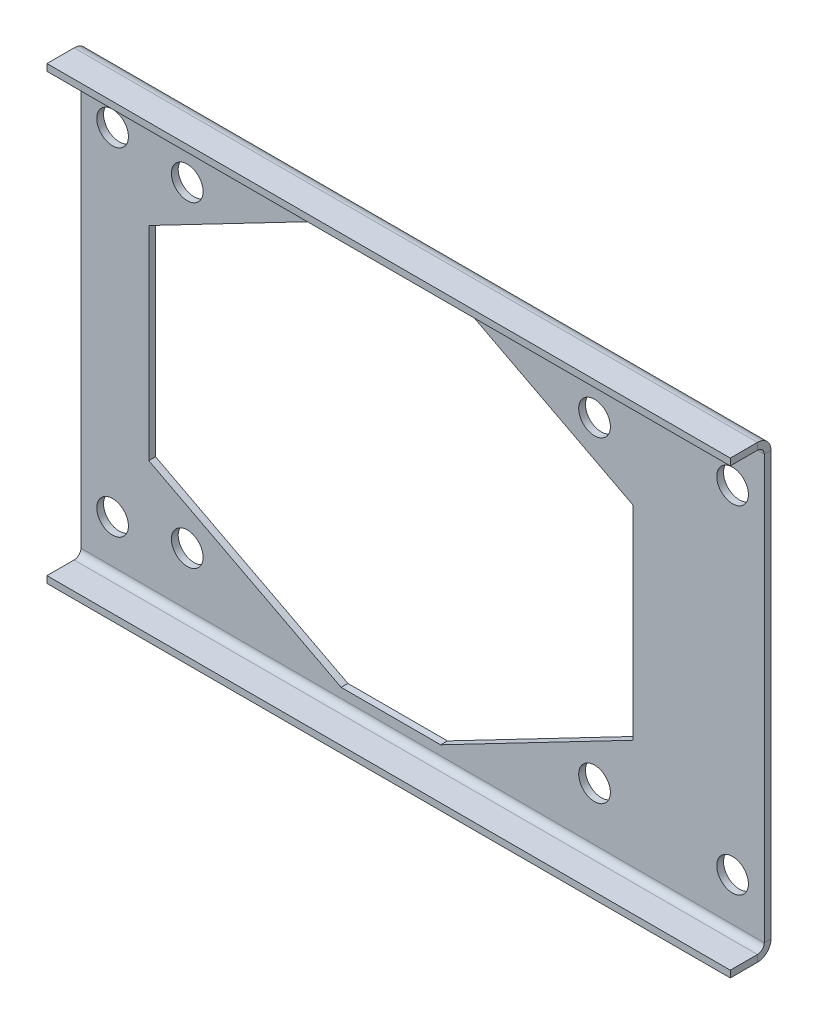
SolidWorks part; units mm, degrees
note: The reader was unsure of these and kept them because the rebuilt part matched: flange length of "Ребро-кромка1".
material "AISI 304"
ref_plane "Спереди" through (0, 0, 0) normal (0, 0, 1) x (1, 0, 0)
ref_plane "Сверху" through (0, 0, 0) normal (0, 1, 0) x (1, 0, 0)
ref_plane "Справа" through (0, 0, 0) normal (1, 0, 0) x (0, 0, -1)
sketch "Эскиз1" plane through (0, 0, 0) normal (0, 0, 1) x (1, 0, 0)
  line L0 (-151, 0) -> (151, 0)
  line L1 (-151, 0) -> (-151, 96.5)
  line L2 (-151, 96.5) -> (-121, 96.5)
  line L5 (93, 96.5) -> (151, 96.5)
  line L6 (151, 96.5) -> (151, 0)
  line L7 (-121, 96.5) -> (-121, 51.5)
  line L8 (-121, 51.5) -> (-36, 7.25)
  line L9 (-36, 7.25) -> (8, 7.25)
  line L10 (8, 7.25) -> (93, 51.5)
  line L11 (93, 51.5) -> (93, 96.5)
  dimension "D4" = 45
  dimension "D1" = 302
  dimension "D2" = 96.5
  dimension "D3" = 214
  dimension "D5" = 30
  dimension "D6" = 44
  dimension "D7" = 89.25
base flange "Базовая кромка1" sketch "Эскиз1" thickness 3 reverse thickness direction no parameters "D1"=3
edge flange "Ребро-кромка1" sketch "Эскиз8" flange angle 90 flange length 15 flange position material outside bend radius 3 thickness 3 relief rectangular parameters "D1"=2, "D6"=10
sketch "Эскиз8" plane through (0, 0, 0) normal (0, -1, 0) x (1, 0, 0)
  line L2 (-151, 0) -> (-151, 15)
  line L3 (-151, 15) -> (151, 15)
  line L4 (151, 15) -> (151, 0)
  line L7 (-151, 0) -> (151, 0) construction
  line L8 (-151, 0) -> (151, 0)
bend "EdgeBend1" bend radius 3 bend angle 90 parameters "D5"=1
mirror "Зеркальное отражение1" about plane through (-151, 96.5, -3) normal (0, 1, 0) of bodies 104
bend "Зеркальное отражение сгиба1" bend radius 3 bend angle 90 parameters "D5"=2
sketch "Эскиз9" plane through (0, 0, -3) normal (0, 0, -1) x (-1, 0, 0)
  line L0 (151, 190) -> (151, 3) construction
  line L1 (-151, 196) -> (151, 196) construction
  line L2 (-151, -3) -> (151, -3) construction
  line L3 (0, 50) -> (0, -50) construction
  circle A0 centre (137, 171) radius 7
  circle A1 centre (137, 22) radius 7
  circle A2 centre (-137, 22) radius 7
  circle A3 centre (-137, 171) radius 7
  dimension "D1" = 14
  dimension "D2" = 14
  dimension "D3" = 25
  dimension "D4" = 25
extrude "Вырез-Вытянуть1" cut sketch "Эскиз9" against normal blind 10
sketch "Эскиз10" plane through (0, 0, 0) normal (0, 0, 1) x (1, 0, 0)
  line L1 (151, -3) -> (-151, -3) construction
  line L2 (151, 3) -> (151, 190) construction
  line L3 (151, 196) -> (-151, 196) construction
  circle A0 centre (76, 166.5) radius 7
  circle A1 centre (-104, 166.5) radius 7
  circle A2 centre (-104, 26.5) radius 7
  circle A3 centre (76, 26.5) radius 7
  dimension "D1" = 75
  dimension "D2" = 29.5
  dimension "D3" = 14
  dimension "D6" = 140
  dimension "D7" = 180
  dimension "D8" = 29.5
  dimension "D4" = 2
  dimension "D5" = 2
extrude "Вырез-Вытянуть2" cut sketch "Эскиз10" against normal blind 3 normal cut yes
sketch "Сгиб-Линии1" [suppressed] plane through (0, 0, 0) normal (0, 1, 0) x (1, 0, 0)
sketch "Граничная рамка1" [suppressed] plane through (0, 0, 0) normal (0, 1, 0) x (1, 0, 0)
sheet metal parameters "Листовой металл3" thickness 3 parameters "D1"=2
flat pattern "Развертка3" [suppressed]
sketch "Сгиб-Линии2" plane through (0, 0, 0) normal (0, 1, 0) x (1, 0, 0)
sketch "Граничная рамка2" [suppressed] plane through (0, 0, 0) normal (0, 1, 0) x (1, 0, 0)
sheet metal parameters "Листовой металл4" thickness 3 parameters "D1"=2
flat pattern "Развертка3" [suppressed]
sketch "Сгиб-Линии2" plane through (0, 0, 0) normal (0, 1, 0) x (1, 0, 0)
sketch "Граничная рамка2" [suppressed] plane through (0, 0, 0) normal (0, 1, 0) x (1, 0, 0)
bend of the flat pattern "Плоское состояние-<EdgeBend1>1"
sheet metal parameters "Листовой металл5" thickness 3 parameters "D1"=2
flat pattern "Развертка5" [suppressed]
sketch "Сгиб-Линии3" plane through (0, 0, 0) normal (0, 1, 0) x (1, 0, 0)
sketch "Граничная рамка3" [suppressed] plane through (0, 0, 0) normal (0, 1, 0) x (1, 0, 0)
bend of the flat pattern "Плоское состояние-<EdgeBend1>2"
bend of the flat pattern "Плоское состояние-<Зеркальное отражение сгиба1>1"
sheet metal parameters "Листовой металл6" thickness 3 parameters "D1"=2
flat pattern "Развертка5" [suppressed]
sketch "Сгиб-Линии3" plane through (0, 0, 0) normal (0, 1, 0) x (1, 0, 0)
sketch "Граничная рамка3" [suppressed] plane through (0, 0, 0) normal (0, 1, 0) x (1, 0, 0)
bend of the flat pattern "Плоское состояние-<EdgeBend1>2"
bend of the flat pattern "Плоское состояние-<Зеркальное отражение сгиба1>1"
sheet metal parameters "Листовой металл7" thickness 3 parameters "D1"=2
flat pattern "Развертка5"
sketch "Сгиб-Линии3" plane through (0, 0, 0) normal (0, 0, 1) x (1, 0, 0)
  line L0 (151, 193.5343) -> (-151, 193.5343) construction
  line L1 (-151, -0.5343) -> (151, -0.5343) construction
  line L2 (151, 193.5343) -> (-151, 193.5343) construction
  line L3 (-151, -0.5343) -> (151, -0.5343) construction
sketch3d "Граничная рамка3" [suppressed]
  line L0 (-151, -16.0686, 0) -> (151, -16.0686, 0) construction
  line L1 (-151, 209.0686, 0) -> (151, 209.0686, 0) construction
  line L2 (-151, -16.0686, 0) -> (-151, 209.0686, 0) construction
  line L3 (151, -16.0686, 0) -> (151, 209.0686, 0) construction
bend of the flat pattern "Плоское состояние-<EdgeBend1>2"
bend of the flat pattern "Плоское состояние-<Зеркальное отражение сгиба1>1"
